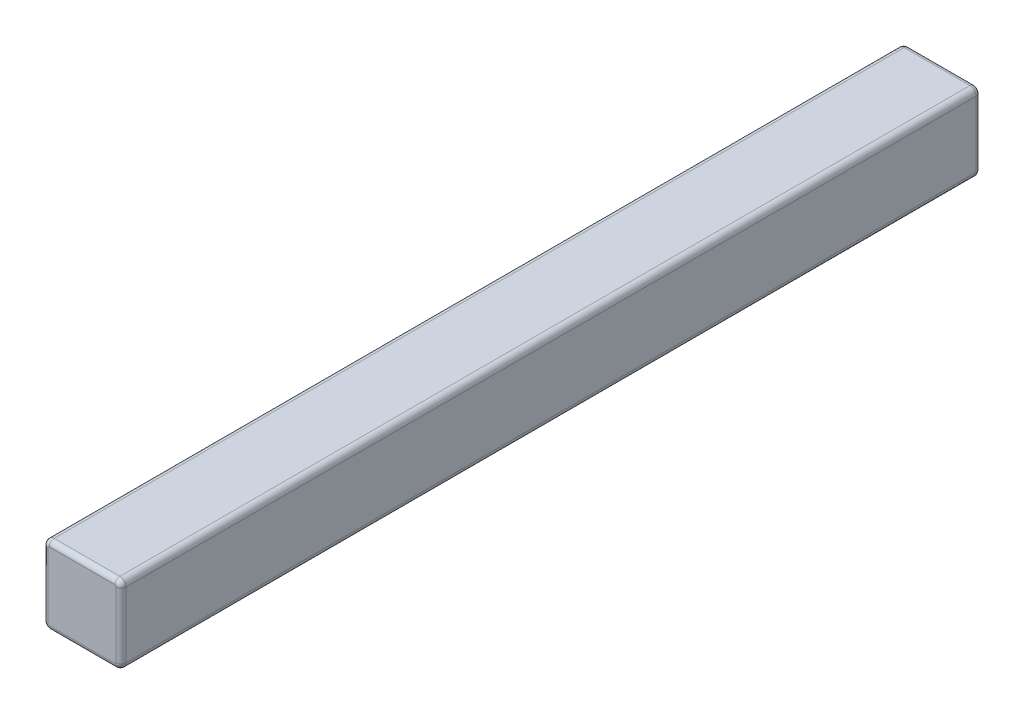
SolidWorks part; units mm, degrees
material "Plain Carbon Steel"
ref_plane "Front Plane" through (0, 0, 0) normal (0, 0, 1) x (1, 0, 0)
ref_plane "Top Plane" through (0, 0, 0) normal (0, 1, 0) x (1, 0, 0)
ref_plane "Right Plane" through (0, 0, 0) normal (1, 0, 0) x (0, 0, -1)
sketch "Sketch1" plane through (0, 0, 0) normal (0, 0, 1) x (1, 0, 0)
  line L1 (-1.3375, 1.5875) -> (1.3375, 1.5875)
  line L2 (-1.5875, 1.3375) -> (-1.5875, -1.3375)
  line L3 (-1.3375, -1.5875) -> (1.3375, -1.5875)
  line L4 (1.5875, 1.3375) -> (1.5875, -1.3375)
  line L5 (-1.5875, 1.5875) -> (1.5875, -1.5875) construction
  line L6 (-1.5875, -1.5875) -> (1.5875, 1.5875) construction
  arc A0 (-1.5875, -1.3375) -> (-1.3375, -1.5875) centre (-1.3375, -1.3375) ccw
  arc A1 (1.3375, -1.5875) -> (1.5875, -1.3375) centre (1.3375, -1.3375) ccw
  arc A2 (1.5875, 1.3375) -> (1.3375, 1.5875) centre (1.3375, 1.3375) ccw
  arc A3 (-1.3375, 1.5875) -> (-1.5875, 1.3375) centre (-1.3375, 1.3375) ccw
  point P0 (0, 0)
  dimension "D2" = 0.25
  dimension "D1" = 3.175
extrude "Boss-Extrude1" add sketch "Sketch1" along normal blind 35 contours L1 A2 L4 A1 L3 A0 L2 A3
fillet "Fillet1" radius 0.2 16 edges at (-1.5875, 0, 0) (-1.5143, -1.5143, 0) (0, -1.5875, 0) (1.5143, -1.5143, 0) (1.5875, 0, 0) (1.5143, 1.5143, 0) (0, 1.5875, 0) (-1.5143, 1.5143, 0) (0, 1.5875, 35) (1.5143, 1.5143, 35) (1.5875, 0, 35) (1.5143, -1.5143, 35) (0, -1.5875, 35) (-1.5143, -1.5143, 35) (-1.5875, 0, 35) (-1.5143, 1.5143, 35)
ref_axis "Axis1" through (0, 0, 0) along (0, 0, 1)
